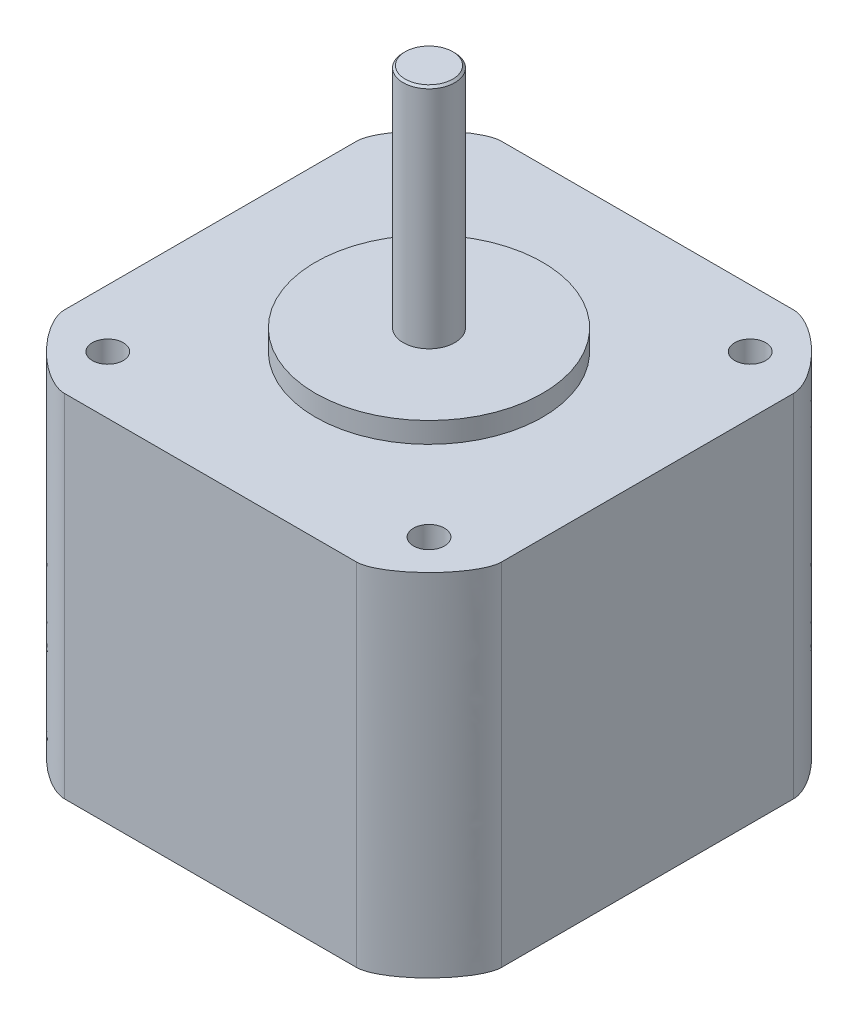
SolidWorks part; units mm, degrees
note: The reader was unsure of these and kept them because the rebuilt part matched: shared geometry of "Sketch1<3>", "Sketch3<2>".
ref_plane "Front" through (0, 0, 0) normal (0, 0, 1) x (1, 0, 0)
ref_plane "Top" through (0, 0, 0) normal (0, 1, 0) x (1, 0, 0)
ref_plane "Right" through (0, 0, 0) normal (1, 0, 0) x (0, 0, -1)
sketch "Sketch1" plane through (0, 0, 0) normal (0, 1, 0) x (1, 0, 0)
  line L1 (-21.15, -21.15) -> (21.15, -21.15)
  line L2 (-21.15, -21.15) -> (-21.15, 21.15)
  line L3 (-21.15, 21.15) -> (21.15, 21.15)
  line L4 (21.15, -21.15) -> (21.15, 21.15)
  line L5 (-21.15, -21.15) -> (21.15, 21.15) construction
  line L6 (-21.15, 21.15) -> (21.15, -21.15) construction
  line L7 (-15.55, -15.55) -> (15.55, -15.55) construction
  line L8 (-15.55, -15.55) -> (-15.55, 15.55) construction
  line L9 (-15.55, 15.55) -> (15.55, 15.55) construction
  line L10 (15.55, -15.55) -> (15.55, 15.55) construction
  line L11 (-15.55, -15.55) -> (15.55, 15.55) construction
  line L12 (-15.55, 15.55) -> (15.55, -15.55) construction
  circle A0 centre (-15.55, 15.55) radius 1.5
  circle A1 centre (15.55, 15.55) radius 1.5
  circle A2 centre (15.55, -15.55) radius 1.5
  circle A3 centre (-15.55, -15.55) radius 1.5
  point P0 (0, 0)
  point P6 (0, 0)
  dimension "D3" = 3
  dimension "D1" = 42.3
  dimension "D2" = 31.1
extrude "Boss-Extrude1" add sketch "Sketch1" against normal blind 34 contours L1 L4 L3 L2 A3 A2 A1 A0 | A2 | A1 | A0
fillet "Fillet1" radius 7 4 edges at (21.15, -17, 21.15) (21.15, -17, -21.15) (-21.15, -17, 21.15) (-21.15, -17, -21.15)
extrude "Cut-Extrude1" cut sketch "Sketch1<3>" against normal blind 4 contours A3 | A0 | A1 | A2
sketch "Sketch1<3>" plane through (0, 0, 0) normal (0, 1, 0) x (1, 0, 0) same geometry as "Sketch1"
sketch "Sketch3" plane through (0, 0, 0) normal (0, 1, 0) x (1, 0, 0)
  circle A0 centre (0, 0) radius 11
  circle A1 centre (0, 0) radius 2.5
  dimension "D1" = 22
  dimension "D2" = 5
extrude "Boss-Extrude2" add sketch "Sketch3" along normal blind 2
extrude "Boss-Extrude3" add sketch "Sketch3<2>" along normal blind 24 contours A1
sketch "Sketch3<2>" plane through (0, 0, 0) normal (0, 1, 0) x (1, 0, 0) same geometry as "Sketch3"
chamfer "Chamfer1" distance 0.2 angle 45 1 edges at (0, 24, 2.5)
